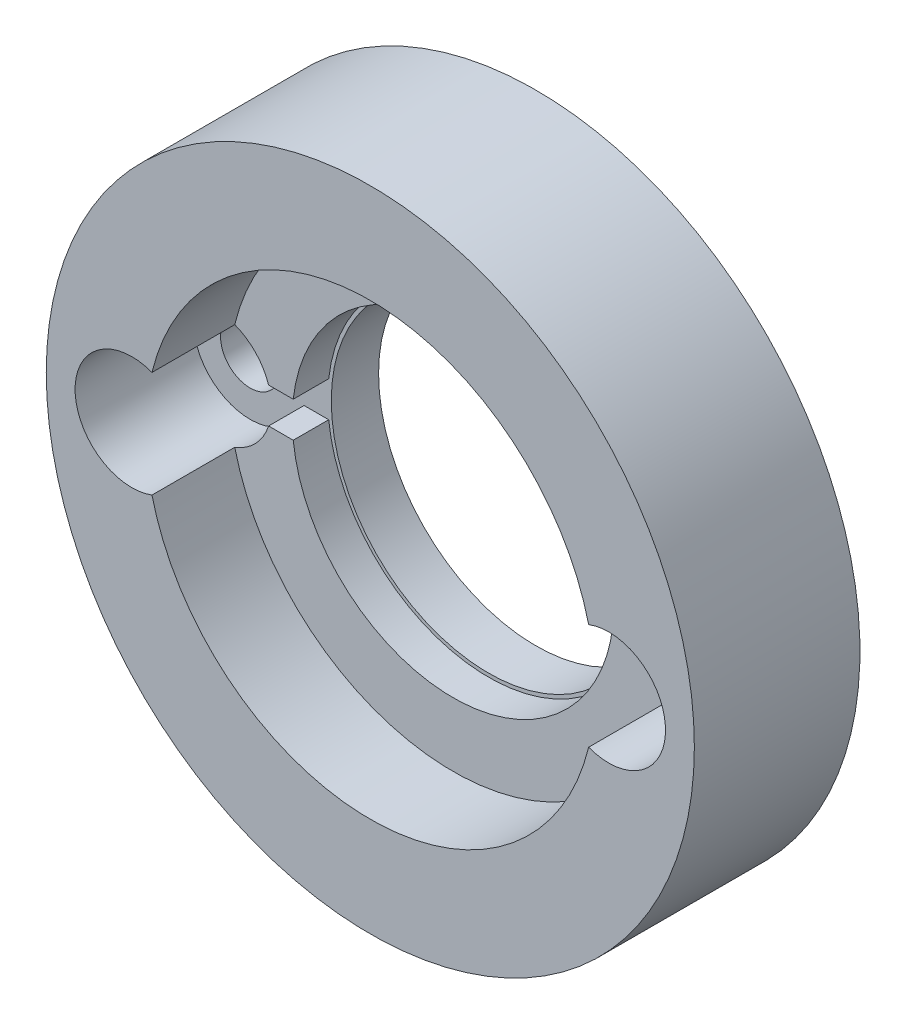
SolidWorks part; units mm, degrees
ref_plane "Alzado" through (0, 0, 0) normal (0, 0, 1) x (1, 0, 0)
ref_plane "Planta" through (0, 0, 0) normal (0, 1, 0) x (1, 0, 0)
ref_plane "Vista lateral" through (0, 0, 0) normal (1, 0, 0) x (0, 0, -1)
sketch "Croquis1" plane through (0, 0, 0) normal (0, 0, 1) x (1, 0, 0)
  line L0 (0, 8.3596) -> (0, -1.3417) construction
  line L1 (9, 0.75) -> (-9, 0.75)
  line L2 (0, 0.75) -> (0, -0.75)
  line L3 (9, -0.75) -> (-9, -0.75)
  line L4 (-9, 0.75) -> (-9, -0.75)
  line L5 (-12.48, 10.7299) -> (-12.48, -4.9079) construction
  line L6 (9, 0.75) -> (9, -0.75)
  line L7 (0, 0) -> (-17.6562, 0) construction
  circle A0 centre (-10.08, 0) radius 2.4
  circle A1 centre (-10.08, 0) radius 0.9
  circle A2 centre (10.08, 0) radius 0.9
  circle A3 centre (10.08, 0) radius 2.4
  circle A4 centre (0, 0) radius 13.7
  point P9 (0, 0)
  dimension "D1" = 1.8
  dimension "D4" = 4.8
  dimension "D6" = 27.4
  dimension "D2" = 1.5
  dimension "D3" = 9
  dimension "D5" = 12.48
extrude "Saliente-Extruir1" add sketch "Croquis1" along normal blind 5 contours A4 L1 A3 L3 A0 region at (-13.3125, 0, 0)
sketch "Croquis2" plane through (0, 0, 5) normal (0, 0, 1) x (1, 0, 0)
  circle A0 centre (0, 0) radius 9.5
  dimension "D1" = 19
extrude "Cortar-Extruir1" cut sketch "Croquis2" against normal blind 3.5
sketch "Croquis3" plane through (0, 0, 1.5) normal (0, 0, 1) x (1, 0, 0)
  circle A0 centre (0, 0) radius 6.8
  dimension "D1" = 13.6
extrude "Cortar-Extruir2" cut sketch "Croquis3" against normal blind 3
sketch "Croquis4" plane through (0, 0, 0) normal (0, 0, -1) x (-1, 0, 0)
  circle A0 centre (0, 0) radius 13.7 construction
  circle A1 centre (0, 0) radius 13.7
  circle A2 centre (0, 0) radius 6.65
  dimension "D1" = 13.3
extrude "Saliente-Extruir2" add sketch "Croquis4" along normal blind 2
sketch "Croquis5" plane through (0, 0, 5) normal (0, 0, 1) x (1, 0, 0)
  circle A0 centre (-10.08, 0) radius 1.25
  circle A1 centre (10.08, 0) radius 1.25
  dimension "D1" = 2.5
  dimension "D2" = 2.5
extrude "Cortar-Extruir3" cut sketch "Croquis5" against normal through all
